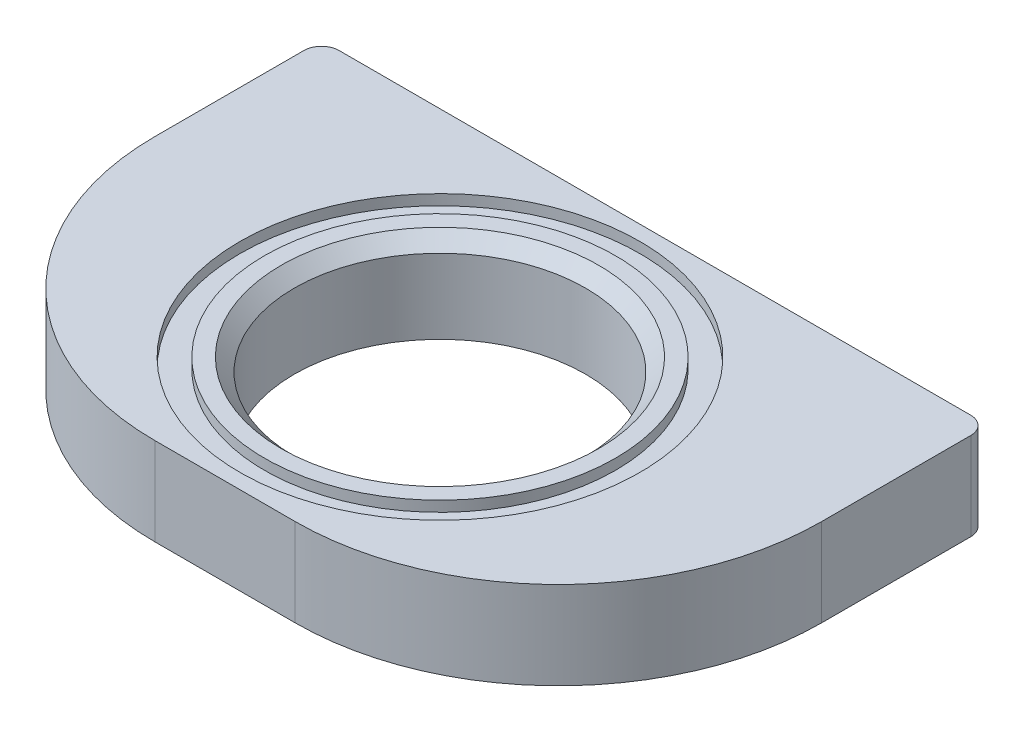
SolidWorks part; units mm, degrees
ref_plane "Front Plane" through (0, 0, 0) normal (0, 0, 1) x (1, 0, 0)
ref_plane "Top Plane" through (0, 0, 0) normal (0, 1, 0) x (1, 0, 0)
ref_plane "Right Plane" through (0, 0, 0) normal (1, 0, 0) x (0, 0, -1)
sketch "Sketch1" plane through (0, 0, 0) normal (0, 1, 0) x (1, 0, 0)
  line L1 (-19, 12.25) -> (19, 12.25)
  line L2 (-19, 12.25) -> (-19, -12.25)
  line L3 (-19, -12.25) -> (19, -12.25)
  line L4 (19, 12.25) -> (19, -12.25)
  circle A0 centre (0, 0) radius 8.3
  dimension "D5" = 16.6
  dimension "D1" = 38
  dimension "D2" = 24.5
  dimension "D3" = 12.25
  dimension "D4" = 19
extrude "Boss-Extrude1" add sketch "Sketch1" along normal blind 5
fillet "Fillet1" radius 15 2 edges at (19, 2.5, 12.25) (-19, 2.5, 12.25)
fillet "Fillet2" radius 1 2 edges at (-19, 2.5, -12.25) (19, 2.5, -12.25)
chamfer "Chamfer1" distance 0.75 angle 45 1 edges at (0, 5, 8.3)
sketch "Sketch2" plane through (0, 5, 0) normal (0, 1, 0) x (1, 0, 0)
  circle A0 centre (0, 0) radius 10.8807
sketch "Sketch3" plane through (0, 0, 0) normal (0, 0, 1) x (1, 0, 0)
  line L0 (18, 5) -> (-18, 5) construction
  line L1 (-10, 5.5513) -> (-11.4, 5.5513)
  line L2 (-10, 5.5513) -> (-10, 4.4)
  line L3 (-10, 4.4) -> (-11.4, 4.4)
  line L4 (-11.4, 5.5513) -> (-11.4, 4.4)
  dimension "D1" = 10
  dimension "D2" = 0.6
  dimension "D3" = 1.4
sketch "Sketch4" plane through (0, 5, 0) normal (0, 1, 0) x (1, 0, 0)
  circle A0 centre (0, 0) radius 11
sweep "o-ring" cut profiles "Sketch3" path "Sketch4"
